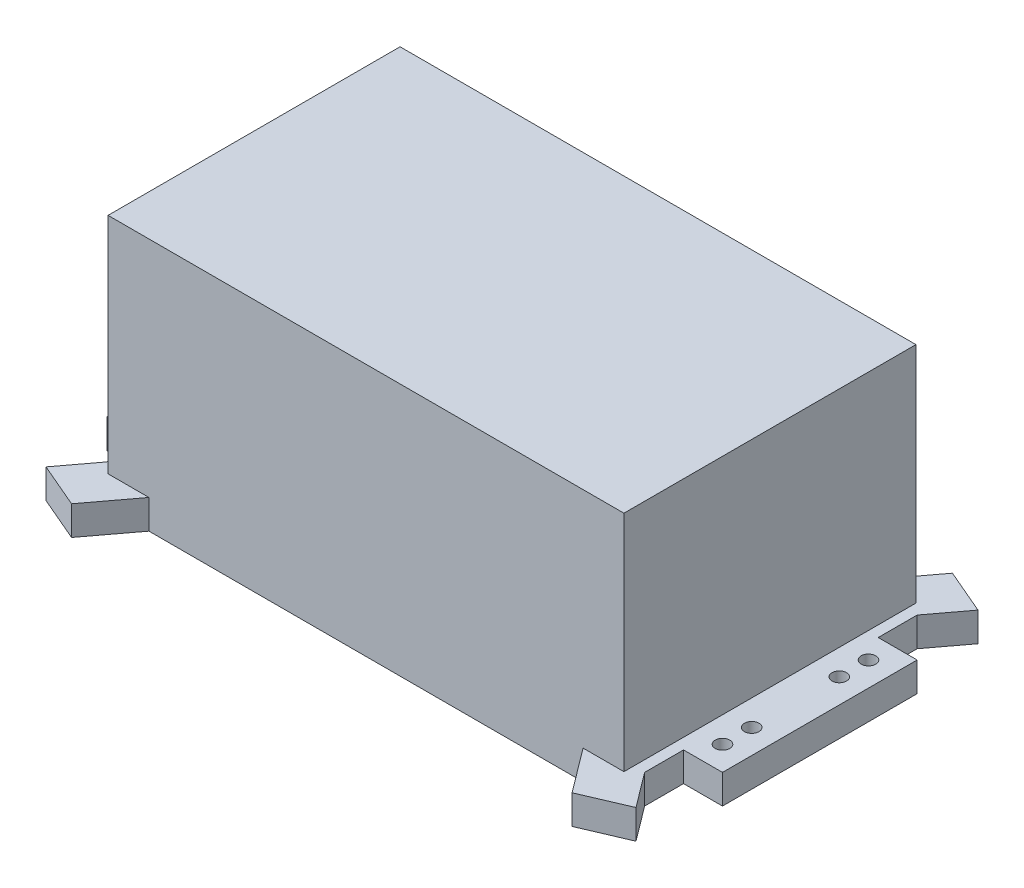
SolidWorks part; units mm, degrees
ref_plane "前视基准面" through (0, 0, 0) normal (0, 0, 1) x (1, 0, 0)
ref_plane "上视基准面" through (0, 0, 0) normal (0, 1, 0) x (1, 0, 0)
ref_plane "右视基准面" through (0, 0, 0) normal (1, 0, 0) x (0, 0, -1)
sketch "草图1" plane through (0, 0, 0) normal (0, 1, 0) x (1, 0, 0)
  line L0 (-65.7171, 0) -> (87.7991, 0) construction
  line L1 (44.6018, -30) -> (-44.6018, -30)
  line L3 (44.6018, 30) -> (-44.6018, 30)
  line L5 (53, -30) -> (-53, 30) construction
  line L6 (53, 30) -> (-53, -30) construction
  line L8 (63.25, -20) -> (63.25, 20)
  line L10 (-63.25, -20) -> (-63.25, 20)
  line L11 (63.25, 20) -> (55.25, 20)
  line L12 (55.25, 20) -> (55.25, 28)
  line L13 (55.25, 28) -> (60.6154, 35.1388)
  line L14 (60.6154, 35.1388) -> (51.4231, 39.0759)
  line L15 (51.4231, 39.0759) -> (44.6018, 30)
  line L16 (63.25, -20) -> (55.25, -20)
  line L17 (55.25, -20) -> (55.25, -28)
  line L18 (55.25, -28) -> (60.6154, -35.1388)
  line L19 (60.6154, -35.1388) -> (51.4231, -39.0759)
  line L20 (51.4231, -39.0759) -> (44.6018, -30)
  line L21 (0, -33.7082) -> (0, 42.5182) construction
  line L22 (-51.4231, -39.0759) -> (-44.6018, -30)
  line L23 (-60.6154, -35.1388) -> (-51.4231, -39.0759)
  line L24 (-55.25, -28) -> (-60.6154, -35.1388)
  line L25 (-55.25, -20) -> (-55.25, -28)
  line L26 (-63.25, -20) -> (-55.25, -20)
  line L27 (-63.25, 20) -> (-55.25, 20)
  line L28 (-55.25, 20) -> (-55.25, 28)
  line L29 (-55.25, 28) -> (-60.6154, 35.1388)
  line L30 (-51.4231, 39.0759) -> (-44.6018, 30)
  line L31 (-60.6154, 35.1388) -> (-51.4231, 39.0759)
  circle A0 centre (58.25, 15) radius 1.5
  circle A1 centre (-58.25, 15) radius 1.5
  circle A2 centre (58.25, 9) radius 1.5
  circle A3 centre (-58.25, 9) radius 1.5
  circle A4 centre (58.25, -9) radius 1.5
  circle A5 centre (58.25, -15) radius 1.5
  circle A6 centre (-58.25, -9) radius 1.5
  circle A7 centre (-58.25, -15) radius 1.5
  point P0 (0, 0)
  point P5 (0, 0)
  dimension "D5" = 3
  dimension "D6" = 3
  dimension "D7" = 3
  dimension "D8" = 3
  dimension "D1" = 60
  dimension "D2" = 106
  dimension "D3" = 40
  dimension "D4" = 126.5
  dimension "D9" = 8
  dimension "D10" = 8
  dimension "D11" = 10
extrude "凸台-拉伸1" add sketch "草图1" along normal blind 6
ref_plane "基准面1" through (0, 6, 0) normal (0, 1, 0) x (1, 0, 0)
sketch "草图2" plane through (0, 6, 0) normal (0, 1, 0) x (1, 0, 0)
  line L1 (53, -30) -> (-53, -30)
  line L2 (53, -30) -> (53, 30)
  line L3 (53, 30) -> (-53, 30)
  line L4 (-53, -30) -> (-53, 30)
  line L5 (53, -30) -> (-53, 30) construction
  line L6 (53, 30) -> (-53, -30) construction
  point P0 (0, 0)
  dimension "D1" = 60
  dimension "D2" = 106
extrude "凸台-拉伸2" add sketch "草图2" along normal blind 46
sketch "草图3" plane through (0, 0, -30) normal (0, 0, -1) x (-1, 0, 0)
  line L1 (-42.197, 39.6989) -> (-14.3671, 39.6989)
  line L2 (-42.197, 39.6989) -> (-42.197, 25.4323)
  line L3 (-42.197, 25.4323) -> (-14.3671, 25.4323)
  line L4 (-14.3671, 39.6989) -> (-14.3671, 25.4323)
  line L5 (-12.2572, 39.6989) -> (15.9746, 39.6989)
  line L6 (-12.2572, 39.6989) -> (-12.2572, 25.4323)
  line L7 (-12.2572, 25.4323) -> (15.9746, 25.4323)
  line L8 (15.9746, 39.6989) -> (15.9746, 25.4323)
  line L9 (-36.2693, 15.9882) -> (-30.3416, 15.9882)
  line L10 (-36.2693, 15.9882) -> (-36.2693, 12.9741)
  line L11 (-36.2693, 12.9741) -> (-30.3416, 12.9741)
  line L12 (-30.3416, 15.9882) -> (-30.3416, 12.9741)
  line L13 (-26.2224, 15.9882) -> (-19.491, 15.9882)
  line L14 (-26.2224, 15.9882) -> (-26.2224, 12.0699)
  line L15 (-26.2224, 12.0699) -> (-19.491, 12.0699)
  line L16 (-19.491, 15.9882) -> (-19.491, 12.0699)
  line L17 (-14.3671, 15.9882) -> (-7.6356, 15.9882)
  line L18 (-14.3671, 15.9882) -> (-14.3671, 12.0699)
  line L19 (-14.3671, 12.0699) -> (-7.6356, 12.0699)
  line L20 (-7.6356, 15.9882) -> (-7.6356, 12.0699)
  circle A0 centre (7.2338, 14.9835) radius 2.9136
extrude "切除-拉伸1" cut sketch "草图3" against normal blind 2
